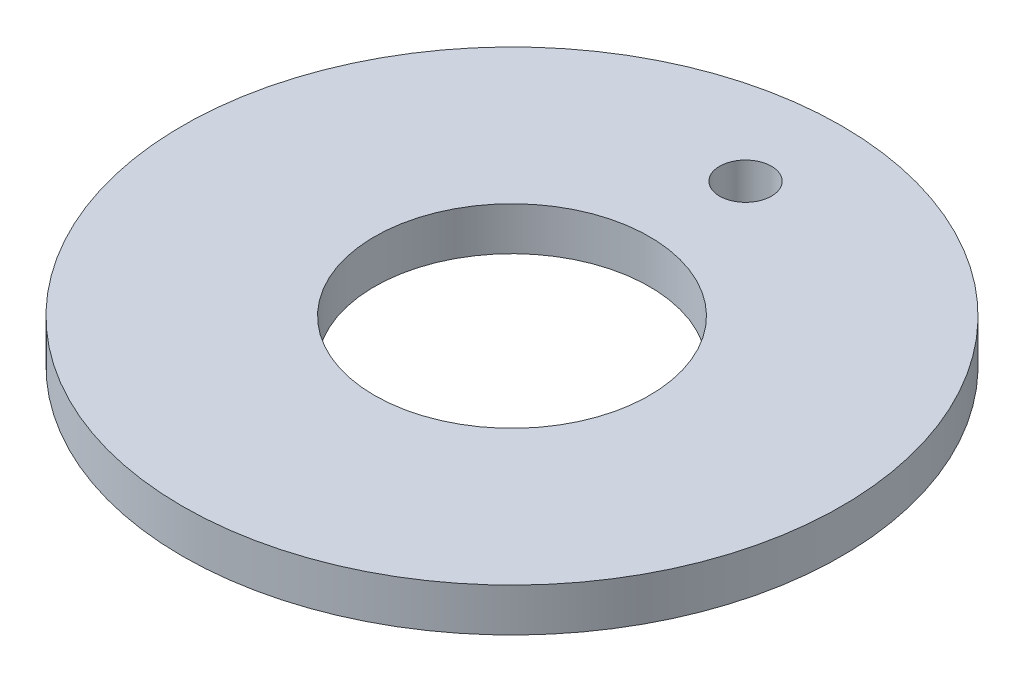
SolidWorks part; units mm, degrees
ref_plane "Front Plane" through (0, 0, 0) normal (0, 0, 1) x (1, 0, 0)
ref_plane "Top Plane" through (0, 0, 0) normal (0, 1, 0) x (1, 0, 0)
ref_plane "Right Plane" through (0, 0, 0) normal (1, 0, 0) x (0, 0, -1)
sketch "Sketch1" plane through (0, 0, 0) normal (0, 1, 0) x (1, 0, 0)
  line L0 (0, 38.1) -> (0, 15.9) construction
  circle A0 centre (0, 0) radius 38.1
  circle A1 centre (0, 0) radius 15.9
  circle A2 centre (0, 27) radius 3
  point P8 (0, 27)
  dimension "D1" = 76.2
  dimension "D2" = 31.8
  dimension "D3" = 6
extrude "Boss-Extrude1" add sketch "Sketch1" along normal blind 5
